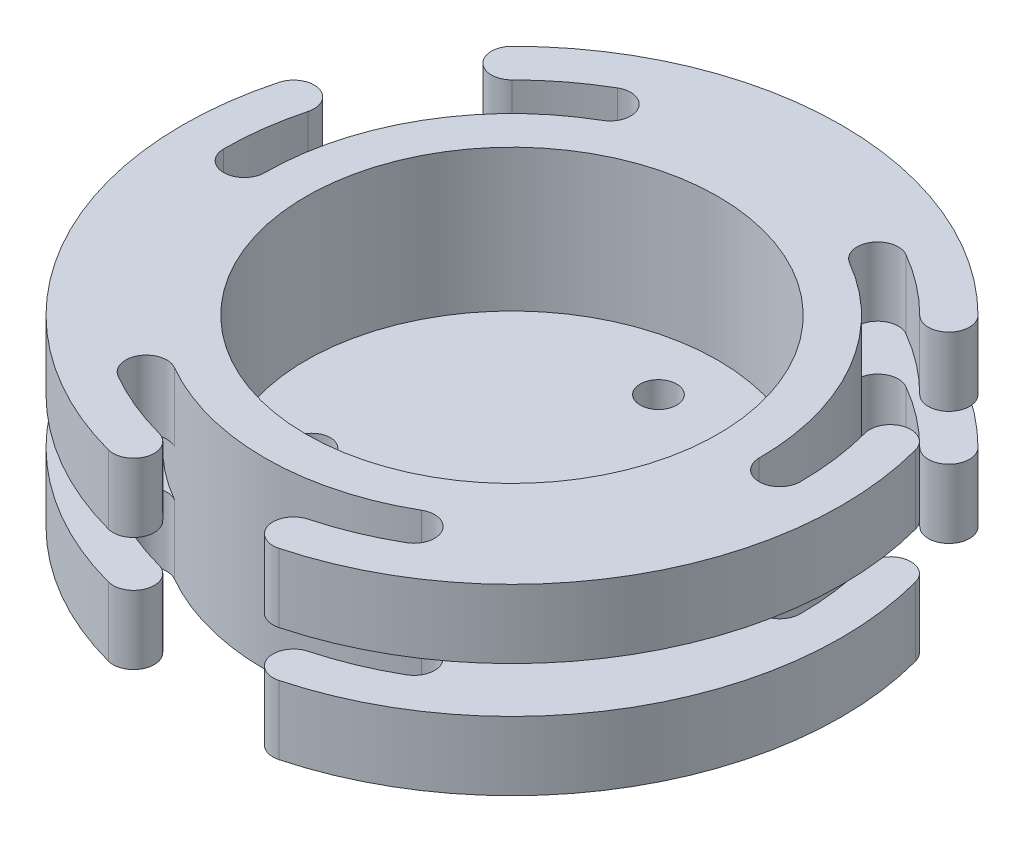
SolidWorks part; units mm, degrees
material "Alliage 1060"
ref_plane "Plan de face" through (0, 0, 0) normal (0, 0, 1) x (1, 0, 0)
ref_plane "Plan de dessus" through (0, 0, 0) normal (0, 1, 0) x (1, 0, 0)
ref_plane "Plan de droite" through (0, 0, 0) normal (1, 0, 0) x (0, 0, -1)
sketch "Esquisse1" plane through (0, 0, 0) normal (0, 1, 0) x (1, 0, 0)
  circle A0 centre (0, 0) radius 22.5
  circle A1 centre (0, 0) radius 40 construction
  circle A2 centre (0, 0) radius 36 construction
  circle A3 centre (0, 0) radius 31.5
  circle A4 centre (0, 0) radius 27 construction
  dimension "D1" = 45
  dimension "D2" = 80
  dimension "D3" = 72
  dimension "D4" = 63
  dimension "D5" = 54
extrude "Boss.-Extru.1" add sketch "Esquisse1" along normal blind 20
sketch "Esquisse2" plane through (0, 20, 0) normal (0, 1, 0) x (1, 0, 0)
  line L0 (-14.625, 25.3312) -> (0, 0) construction
  line L1 (0, 0) -> (-29.25, 0) construction
  line L2 (0, 0) -> (0, 31.5) construction
  arc A0 (-29.25, 0) -> (-14.625, 25.3312) centre (0, 0) cw construction
  arc A1 (-15.75, 27.2798) -> (-31.5, 0) centre (0, 0) ccw
  arc A2 (-13.5, 23.3827) -> (-27, 0) centre (0, 0) ccw
  arc A3 (-13.5, 23.3827) -> (-15.75, 27.2798) centre (-14.625, 25.3312) ccw
  arc A4 (-31.5, 0) -> (-27, 0) centre (-29.25, 0) ccw
  circle A5 centre (0, 0) radius 31.5 construction
  arc A6 (14.625, 25.3312) -> (29.25, 0) centre (0, 0) cw construction
  arc A7 (31.5, 0) -> (15.75, 27.2798) centre (0, 0) ccw
  arc A8 (27, 0) -> (13.5, 23.3827) centre (0, 0) ccw
  arc A9 (27, 0) -> (31.5, 0) centre (29.25, 0) ccw
  arc A10 (15.75, 27.2798) -> (13.5, 23.3827) centre (14.625, 25.3312) ccw
  arc A11 (14.625, -25.3312) -> (-14.625, -25.3312) centre (0, 0) cw construction
  arc A12 (-15.75, -27.2798) -> (15.75, -27.2798) centre (0, 0) ccw
  arc A13 (-13.5, -23.3827) -> (13.5, -23.3827) centre (0, 0) ccw
  arc A14 (-13.5, -23.3827) -> (-15.75, -27.2798) centre (-14.625, -25.3312) ccw
  arc A15 (15.75, -27.2798) -> (13.5, -23.3827) centre (14.625, -25.3312) ccw
  point P4 (-25.3312, 14.625)
  point P21 (25.3312, 14.625)
  point P28 (0, -29.25)
  point P33 (0, 0)
  dimension "D1" = 2.25
  dimension "D2" = 60
  dimension "D3" = 30
  dimension "D4" = 3
extrude "Enlèv. mat.-Extru.1" cut sketch "Esquisse2" against normal through all
sketch "Esquisse3" plane through (0, 20, 0) normal (0, 1, 0) x (1, 0, 0)
  line L0 (0, 33.75) -> (0, 0) construction
  line L1 (-23.8649, 23.8649) -> (0, 0) construction
  arc A0 (-23.8649, 23.8649) -> (23.8649, 23.8649) centre (0, 0) cw construction
  arc A1 (25.4558, 25.4558) -> (-25.4558, 25.4558) centre (0, 0) ccw
  arc A2 (22.2739, 22.2739) -> (-22.2739, 22.2739) centre (0, 0) ccw
  arc A3 (22.2739, 22.2739) -> (25.4558, 25.4558) centre (23.8649, 23.8649) ccw
  arc A4 (-25.4558, 25.4558) -> (-22.2739, 22.2739) centre (-23.8649, 23.8649) ccw
  arc A5 (15.75, 27.2798) -> (-15.75, 27.2798) centre (0, 0) ccw construction
  arc A6 (32.6, 8.7351) -> (8.7351, -32.6) centre (0, 0) cw construction
  arc A7 (9.3175, -34.7733) -> (34.7733, 9.3175) centre (0, 0) ccw
  arc A8 (8.1528, -30.4267) -> (30.4267, 8.1528) centre (0, 0) ccw
  arc A9 (8.1528, -30.4267) -> (9.3175, -34.7733) centre (8.7351, -32.6) ccw
  arc A10 (34.7733, 9.3175) -> (30.4267, 8.1528) centre (32.6, 8.7351) ccw
  arc A11 (-8.7351, -32.6) -> (-32.6, 8.7351) centre (0, 0) cw construction
  arc A12 (-34.7733, 9.3175) -> (-9.3175, -34.7733) centre (0, 0) ccw
  arc A13 (-30.4267, 8.1528) -> (-8.1528, -30.4267) centre (0, 0) ccw
  arc A14 (-30.4267, 8.1528) -> (-34.7733, 9.3175) centre (-32.6, 8.7351) ccw
  arc A15 (-9.3175, -34.7733) -> (-8.1528, -30.4267) centre (-8.7351, -32.6) ccw
  point P4 (0, 33.75)
  point P19 (29.2284, -16.875)
  point P26 (-29.2284, -16.875)
  point P31 (0, 0)
  dimension "D1" = 2.25
  dimension "D2" = 45
extrude "Boss.-Extru.2" add sketch "Esquisse3" against normal up to surface (20 mm away) up to face at (0, 0, 0)
sketch "Esquisse4" plane through (0, 0, 0) normal (0, -1, 0) x (1, 0, 0)
  circle A0 centre (0, 0) radius 22.5
extrude "Boss.-Extru.3" add sketch "Esquisse4" against normal blind 4.5
sketch "Esquisse5" plane through (0, 4.5, 0) normal (0, 1, 0) x (1, 0, 0)
  line L0 (0, 0) -> (0, 16) construction
  circle A0 centre (0, 16) radius 2
  circle A1 centre (13.8564, -8) radius 2
  circle A2 centre (-13.8564, -8) radius 2
  point P12 (0, 0)
  dimension "D2" = 4
  dimension "D1" = 16
  dimension "D3" = 3
extrude "Enlèv. mat.-Extru.2" cut sketch "Esquisse5" against normal up to next
sketch "Esquisse6" plane through (0, 0, 0) normal (1, 0, 0) x (0, 0, -1)
  line L0 (36, 10) -> (0, 10) construction
  line L1 (36, 12.5) -> (27, 12.5)
  line L2 (36, 12.5) -> (36, 7.5)
  line L3 (36, 7.5) -> (27, 7.5)
  line L4 (27, 12.5) -> (27, 7.5)
  line L5 (0, 10) -> (0, 0) construction
  point P8 (27.9762, 6.6813)
  dimension "D1" = 10
  dimension "D2" = 9
  dimension "D3" = 36
  dimension "D4" = 5
revolve "Enlèvement de matière-Révolution1" cut sketch "Esquisse6" angle 360 about L5
